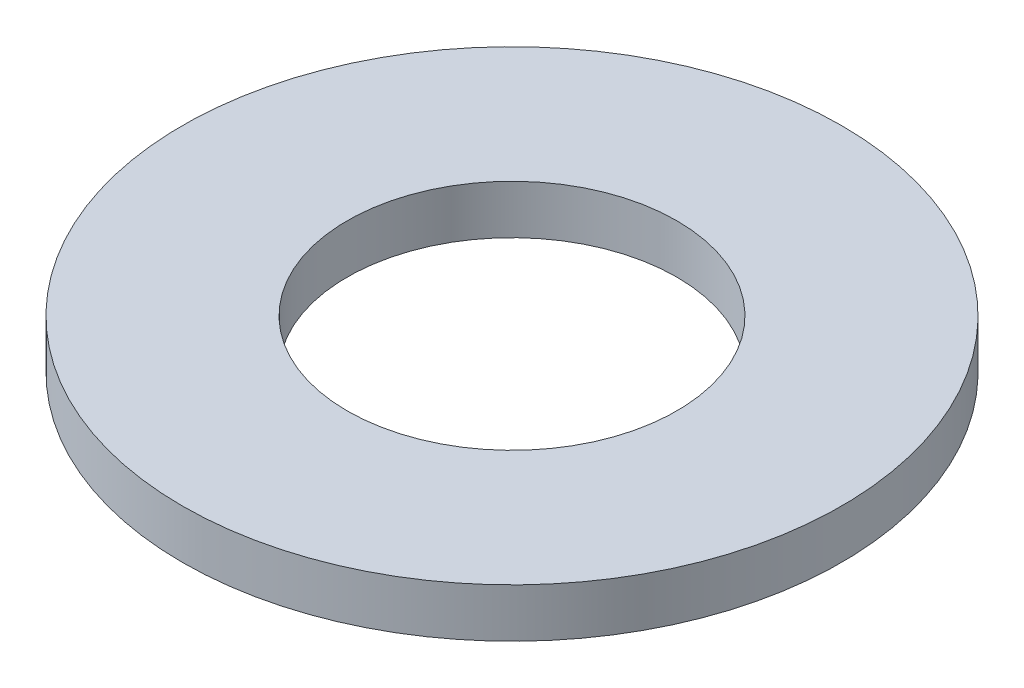
SolidWorks part; units mm, degrees
ref_plane "Front Plane" through (0, 0, 0) normal (0, 0, 1) x (1, 0, 0)
ref_plane "Top Plane" through (0, 0, 0) normal (0, 1, 0) x (1, 0, 0)
ref_plane "Right Plane" through (0, 0, 0) normal (1, 0, 0) x (0, 0, -1)
sketch "Sketch1" plane through (0, 0, 0) normal (0, 1, 0) x (1, 0, 0)
  circle A0 centre (0, 0) radius 4.3688
  circle A1 centre (0, 0) radius 8.7376
  dimension "ID" = 8.7376
  dimension "OD" = 17.4752
sketch "Sketch2" plane through (0, 0, 0) normal (1, 0, 0) x (0, 0, -1)
  line L1 (-8.7376, 0.6477) -> (8.7376, 0.6477)
  line L2 (-8.7376, 0.6477) -> (-8.7376, -0.6477)
  line L3 (-8.7376, -0.6477) -> (8.7376, -0.6477)
  line L4 (8.7376, 0.6477) -> (8.7376, -0.6477)
  line L5 (-8.7376, 0.6477) -> (8.7376, -0.6477) construction
  line L6 (-8.7376, -0.6477) -> (8.7376, 0.6477) construction
  point P0 (0, 0)
  point P6 (8.7376, 0)
  point P7 (-8.7376, 0)
  dimension "Thickness Range [Min]" = 1.2954
sketch "Sketch3" plane through (0, 0, 0) normal (0, 1, 0) x (1, 0, 0)
  circle A0 centre (0, 0) radius 8.7376
  circle A1 centre (0, 0) radius 4.3688
  circle A2 centre (0, 0) radius 8.7376 construction
  circle A3 centre (0, 0) radius 4.3688 construction
extrude "Boss-Extrude1" add sketch "Sketch3" along normal up to vertex (0.6477 mm away) and the other way up to vertex (0.6477 mm away) up to point (0, 0.6477, -8.7376) other way up to point (0, -0.6477, -8.7376)
